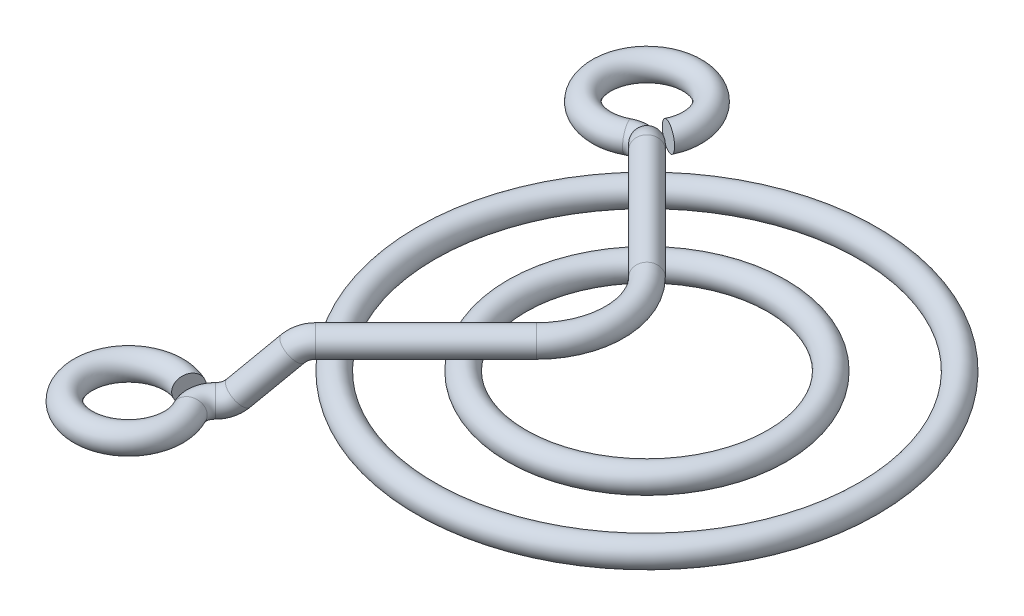
SolidWorks part; units mm, degrees
ref_plane "Front" through (0, 0, 0) normal (0, 0, 1) x (1, 0, 0)
ref_plane "Top" through (0, 0, 0) normal (0, 1, 0) x (1, 0, 0)
ref_plane "Right" through (0, 0, 0) normal (1, 0, 0) x (0, 0, -1)
sketch "Sketch1" plane through (0, 0, 0) normal (0, 0, 1) x (1, 0, 0)
  line L0 (21.56, 0) -> (-21.56, 0) construction
  line L1 (-7.225, 2.4) -> (7.225, 2.4) construction
  line L2 (-14.45, 2.4) -> (14.45, 2.4) construction
  line L3 (0, 2.4) -> (0, 0) construction
  circle A0 centre (-8.025, 4) radius 0.8 construction
  circle A1 centre (-8.025, 2.4) radius 0.8
  circle A2 centre (-13.65, 2.4) radius 0.8
  point P4 (-8.025, 4.8)
  dimension "D2" = 1.6
  dimension "D1" = 4.8
  dimension "D3" = 14.45
  dimension "D4" = 28.9
revolve "Revolve1" add sketch "Sketch1" angle 360 mid plane about L3
sketch "Sketch2" plane through (0, 0, 0) normal (0, 1, 0) x (1, 0, 0)
  line L0 (-10.2248, 10.2248) -> (-3.4142, 3.4142)
  line L1 (0, -2.64) -> (0, 2.64) construction
  line L2 (-2.64, 0) -> (2.64, 0) construction
  line L3 (0, 0) -> (-16, -16) construction
  arc A0 (-3.4142, 3.4142) -> (-2, 0) centre (-6.8284, 0) cw
  circle A1 centre (-2, 0) radius 0.8 construction
  circle A2 centre (0, 0) radius 14.45 construction
  circle A3 centre (-16, 16) radius 2 construction
  circle A4 centre (0, 0) radius 22.6274 construction
  circle A5 centre (-16, -16) radius 2 construction
  circle A6 centre (-16, 16) radius 3.6 construction
  point P9 (-2.8, 0)
  point P10 (-10.2177, 10.2177)
  dimension "D3" = 1.6
  dimension "D5" = 32
  dimension "D6" = 4
  dimension "D7" = 1.6
  dimension "D1" = 45
  dimension "D2" = 2.8
  dimension "D4" = 0.01
sketch "Sketch3" plane through (0, 0, 0) normal (0, 0, 1) x (1, 0, 0)
  circle A0 centre (-2, 4) radius 0.8
  circle A1 centre (-8.025, 4) radius 0.8 construction
sweep "Sweep1" add profiles "Sketch3" path "Sketch2"
ref_plane "Plane1" through (0, 0, 0) normal (0.7071, 0, -0.7071) x (-0.7071, 0, -0.7071)
sketch "Sketch4" plane through (0, 0, 0) normal (0.7071, 0, -0.7071) x (-0.7071, 0, -0.7071)
  line L0 (15.4592, 3.5858) -> (17.8282, 1.2142)
  line L3 (14.46, 3.2) -> (14.46, 4.8) construction
  line L5 (18.8274, 0.8) -> (19.8274, 0.8) construction
  line L10 (19.0274, 0) -> (20.6274, 0) construction
  arc A0 (14.46, 4) -> (15.4592, 3.5858) centre (14.46, 2.5877) cw
  arc A1 (17.8282, 1.2142) -> (18.8274, 0.8) centre (18.8274, 2.2123) ccw
  circle A2 centre (19.8274, 0.8) radius 0.8 construction
  point P9 (19.8274, 0)
  dimension "D1" = 1.4123
  dimension "D3" = 1.6
  dimension "D2" = 1
sketch "Sketch5" plane through (-10.2248, 0, -10.2248) normal (-0.7071, 0, -0.7071) x (-0.7071, 0, 0.7071)
  circle A1 centre (0, 4) radius 0.8
  circle A2 centre (0, 4) radius 0.8
  dimension "D1" = 0
sweep "Sweep2" add profiles "Sketch5" path "Sketch4"
sketch "Sketch6" plane through (0, 0, 0) normal (0, 1, 0) x (1, 0, 0)
  line L0 (-12.7473, 13.8787) -> (-13.8787, 12.7473) construction
  line L2 (-13.4715, 14.7971) -> (-16, 16) construction
  arc A0 (-14.6955, 13.5225) -> (-13.313, 13.313) centre (-14.1464, 12.4796) cw
  arc A2 (-13.4715, 14.7971) -> (-14.6955, 13.5225) centre (-16, 16) ccw
  dimension "D1" = 1.4841
sketch "Sketch7" plane through (-13.313, 0, -13.313) normal (-0.7071, 0, -0.7071) x (-0.7071, 0, 0.7071)
  circle A1 centre (0, 0.8) radius 0.8
  circle A2 centre (0, 0.8) radius 0.8
  dimension "D1" = 0
sweep "Sweep3" add profiles "Sketch7" path "Sketch6"
sketch "Sketch8" plane through (0, 0, 0) normal (0, 1, 0) x (1, 0, 0)
  line L0 (-3.9799, 2.8485) -> (-2.8485, 3.9799)
  line L1 (-2.8485, 3.9799) -> (-3.9799, 2.8485) construction
  line L2 (-2.8485, 3.9799) -> (-9.6591, 10.7904) construction
extrude "Cut-Extrude1" cut sketch "Sketch8" against normal through all and the other way through all flip side to cut
pattern_circular "CirPattern1" count 2 over 90 about axis through (0, 0, 0) along (0, 1, 0) of bodies 114
sketch "Sketch9" plane through (0, 0, 0) normal (0, 1, 0) x (1, 0, 0)
  line L0 (-3.9799, 2.8485) -> (-2.8485, 3.9799) construction
  line L1 (-2.8485, -3.9799) -> (-3.9799, -2.8485) construction
  arc A0 (-3.4142, 3.4142) -> (-3.4142, -3.4142) centre (-6.8284, 0) cw
sketch "Sketch10" plane through (-3.4142, 0, -3.4142) normal (0.7071, 0, 0.7071) x (0.7071, 0, -0.7071)
  circle A1 centre (0, 4) radius 0.8
  circle A2 centre (0, 4) radius 0.8
  dimension "D1" = 0
sweep "Sweep4" add profiles "Sketch10" path "Sketch9"
